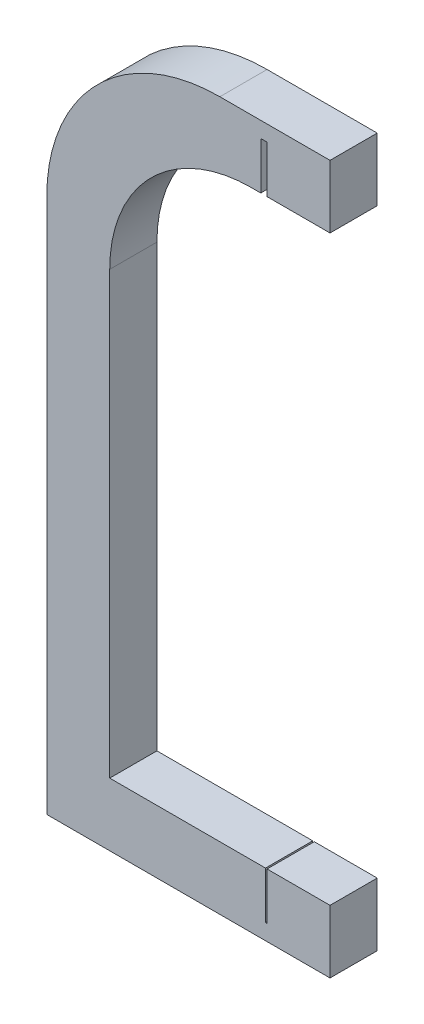
SolidWorks part; units mm, degrees
ref_plane "Front Plane" through (0, 0, 0) normal (0, 0, 1) x (1, 0, 0)
ref_plane "Top Plane" through (0, 0, 0) normal (0, 1, 0) x (1, 0, 0)
ref_plane "Right Plane" through (0, 0, 0) normal (1, 0, 0) x (0, 0, -1)
sketch "Sketch1" plane through (0, 0, 0) normal (0, 0, 1) x (1, 0, 0)
  line L0 (0, 34) -> (0, 0)
  line L1 (0, 0) -> (18, 0)
  line L2 (18, 0) -> (18, 4)
  line L3 (18, 4) -> (4, 4)
  line L4 (4, 4) -> (4, 32)
  line L5 (13, 41) -> (18, 41)
  line L6 (18, 41) -> (18, 45)
  line L7 (18, 45) -> (11, 45)
  arc A0 (11, 45) -> (0, 34) centre (11, 34) ccw
  arc A1 (13, 41) -> (4, 32) centre (13, 32) ccw
  point P11 (0, 45)
  dimension "D6" = 11
  dimension "D7" = 9
  dimension "D3" = 4
  dimension "D4" = 14
  dimension "D5" = 4
extrude "Boss-Extrude1" add sketch "Sketch1" along normal blind 3
sketch "Sketch3" plane through (0, 4, 0) normal (0, 1, 0) x (1, 0, 0)
  line L0 (0, -1.5) -> (13.95, -1.5) construction
  line L1 (0, -3) -> (0, 0) construction
  line L2 (18, 0) -> (4, 0) construction
  line L3 (13.9, -3) -> (14, -3)
  line L4 (13.9, -3) -> (13.9, 0)
  line L5 (13.9, 0) -> (14, 0)
  line L6 (14, -3) -> (14, 0)
  line L7 (13.9, -3) -> (14, 0) construction
  line L8 (13.9, 0) -> (14, -3) construction
extrude "Cut-Extrude1" cut sketch "Sketch3" against normal blind 3
sketch "Sketch4" plane through (0, 41, 0) normal (0, -1, 0) x (1, 0, 0)
  line L0 (0, 1.5) -> (13.8, 1.5) construction
  line L1 (0, 3) -> (0, 0) construction
  line L2 (13, 3) -> (18, 3) construction
  line L3 (13.6, 0) -> (14, 0)
  line L4 (13.6, 0) -> (13.6, 3)
  line L5 (13.6, 3) -> (14, 3)
  line L6 (14, 0) -> (14, 3)
  line L7 (13.6, 0) -> (14, 3) construction
  line L8 (13.6, 3) -> (14, 0) construction
extrude "Cut-Extrude2" cut sketch "Sketch4" against normal blind 3
equation "\"A.L\"= 0.06m"
equation "\"A.h\"= 0.005m"
equation "\"A.d\"= 0.003m"
equation "\"A.delta\"= 45.0001"
equation "\"A.w\"= 0.02m"
equation "\"A.v\"= 0.03m"
equation "\"A.s\"= 0.0075m"
equation "\"A.t\"= 0.005m"
equation "\"B.L\"= 0.04m"
equation "\"B.h\"= 0.004m"
equation "\"B.s\"= 0.008m"
equation "\"B.t\"= 0.004m"
equation "\"C.h\"= 0.0062m"
equation "\"C.d\"= 0.003m"
equation "\"C.L\"= 0.05m"
equation "\"C.wmax\"= 0.005m"
equation "\"D.L\"= 0.045m"
equation "\"D.h\"= 0.004m"
equation "\"D.s\"= 0.01m"
equation "\"D.t\"= 0.004m"
equation "\"a_h\"= 0.0001m"
equation "\"a_d\"= 0.003m"
equation "\"a_L\"= 0.01m"
equation "\"b_h\"= 0.0004m"
equation "\"b_d\"= 0.003m"
equation "\"b_L\"= 0.01m"
equation "\"c_h\"= 0.0001m"
equation "\"c_d\"= 0.003m"
equation "\"c_L\"= 0.01m"
equation "\"d_h\"= 0.0001m"
equation "\"d_d\"= 0.003m"
equation "\"d_L\"= 0.01m"
equation "\"S.h\"= 0.015m"
equation "\"S.L\"= 0.0559m"
equation "\"D1@Sketch1\"=\"D.L\""
equation "\"D2@Sketch1\"=\"D.h\""
equation "\"D3@Sketch1\"=\"D.h\""
equation "\"D4@Sketch1\"=\"D.s\"+0.004"
equation "\"D5@Sketch1\"=\"D.h\""
equation "\"D1@Boss-Extrude1\"=\"A.d\""
equation "\"D1@Sketch3\"=\"D.h\"+\"D.s\"-\"a_h\"/2"
equation "\"D2@Sketch3\"=\"a_h\""
equation "\"D1@Sketch4\"=\"D.h\"+\"D.s\"-\"b_h\"/2"
equation "\"D2@Sketch4\"=\"b_h\""
